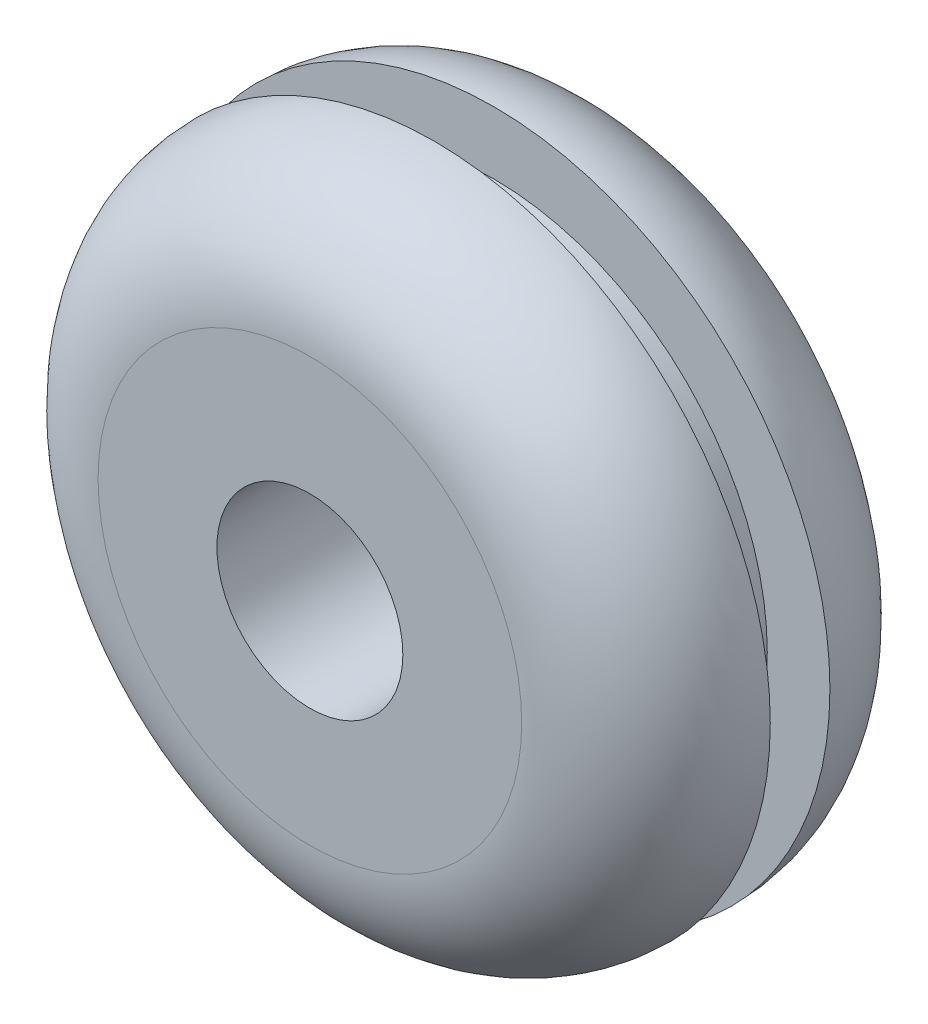
SolidWorks part; units mm, degrees
ref_plane "Plane1" through (0, 0, 0) normal (0, 0, 1) x (1, 0, 0)
ref_plane "Plane2" through (0, 0, 0) normal (0, 1, 0) x (1, 0, 0)
ref_plane "Plane3" through (0, 0, 0) normal (1, 0, 0) x (0, 0, -1)
sketch "Sketch3" plane through (0, 0, 0) normal (0, 0, 1) x (1, 0, 0)
  circle A0 centre (0, 0) radius 6.985
  dimension "D1" = 13.97
extrude "Base-Extrude" add sketch "Sketch3" along normal mid plane 1.524
sketch "Sketch4" plane through (0, 0, 0.762) normal (0, 0, 1) x (1, 0, 0)
  circle A1 centre (0, 0) radius 8.5852
  circle A2 centre (0, 0) radius 8.5852
  dimension "D1" = 1.6002
extrude "Boss-Extrude2" add sketch "Sketch4" along normal blind 3.175
fillet "Fillet1" radius 3.175 1 edges at (8.5852, 0, 3.937)
mirror "Mirror1" about plane through (0, 0, 0) normal (0, 0, 1) of "Fillet1", "Boss-Extrude2"
sketch "Sketch5" plane through (0, 0, 3.937) normal (0, 0, 1) x (1, 0, 0)
  circle A0 centre (0, 0) radius 2.3749
  dimension "D1" = 4.7498
extrude "Cut-Extrude1" cut sketch "Sketch5" against normal through all
